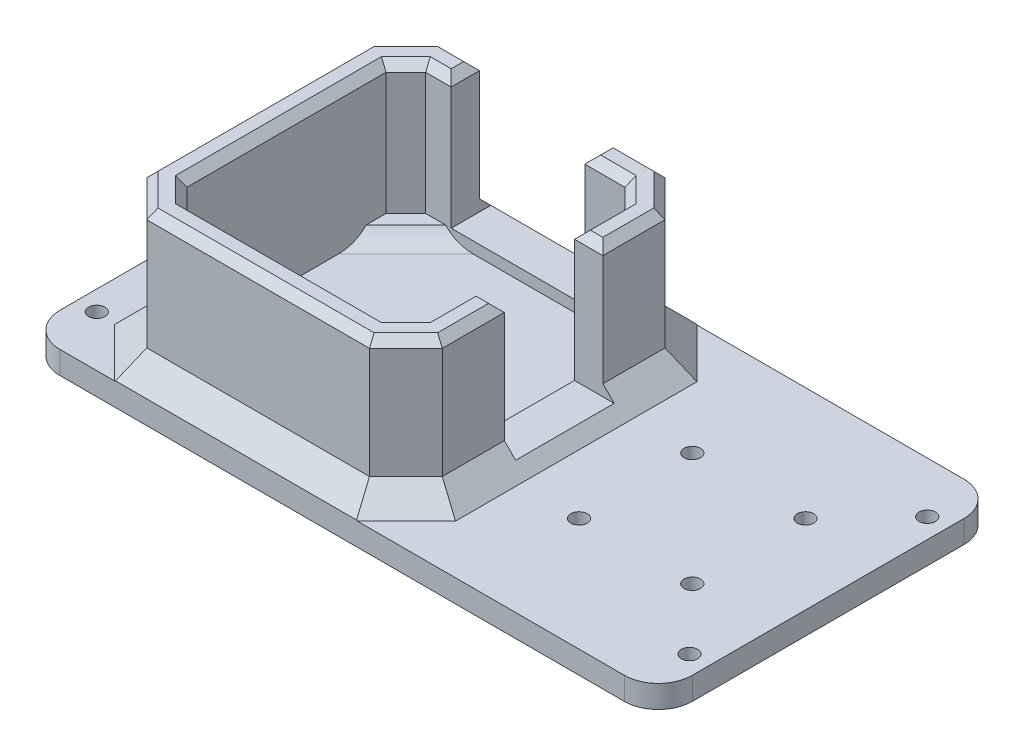
SolidWorks part; units mm, degrees
ref_plane "前视基准面" through (0, 0, 0) normal (0, 0, 1) x (1, 0, 0)
ref_plane "上视基准面" through (0, 0, 0) normal (0, 1, 0) x (1, 0, 0)
ref_plane "右视基准面" through (0, 0, 0) normal (1, 0, 0) x (0, 0, -1)
sketch "草图1" plane through (0, 0, 0) normal (0, 1, 0) x (1, 0, 0)
  line L1 (-52.35, -21) -> (52.35, -21) construction
  line L2 (-52.35, -21) -> (-52.35, 21) construction
  line L3 (-52.35, 21) -> (52.35, 21) construction
  line L4 (52.35, -21) -> (52.35, 21) construction
  line L5 (-52.35, -21) -> (52.35, 21) construction
  line L6 (-52.35, 21) -> (52.35, -21) construction
  line L7 (-55.85, -30) -> (55.85, -30)
  line L8 (-55.85, -30) -> (-55.85, 30)
  line L9 (-55.85, 30) -> (55.85, 30)
  line L10 (55.85, -30) -> (55.85, 30)
  line L11 (-55.85, -30) -> (55.85, 30) construction
  line L12 (-55.85, 30) -> (55.85, -30) construction
  circle A0 centre (-52.35, 21) radius 1.45
  circle A1 centre (52.35, 21) radius 1.45
  circle A2 centre (52.35, -21) radius 1.45
  circle A3 centre (-52.35, -21) radius 1.45
  point P0 (0, 0)
  point P10 (0, 0)
  dimension "D3" = 2.9
  dimension "D4" = 2.9
  dimension "D5" = 2.9
  dimension "D6" = 2.9
  dimension "D1" = 104.7
  dimension "D2" = 42
  dimension "D7" = 3.5
  dimension "D8" = 60
extrude "凸台-拉伸1" add sketch "草图1" along normal blind 4
sketch "草图2" plane through (0, 4, 0) normal (0, 1, 0) x (1, 0, 0)
  line L0 (-55.85, 30) -> (-55.85, -30) construction
  line L5 (-39.85, 21.1) -> (2.35, 21.1)
  line L6 (-39.85, 21.1) -> (-39.85, -21.1)
  line L7 (-39.85, -21.1) -> (2.35, -21.1)
  line L8 (2.35, 21.1) -> (2.35, -21.1)
  line L9 (-39.85, 21.1) -> (2.35, -21.1) construction
  line L10 (-39.85, -21.1) -> (2.35, 21.1) construction
  line L11 (-39.85, 17.6) -> (-36.35, 21.1)
  line L12 (-1.15, -21.1) -> (2.35, -17.6)
  line L13 (-39.85, -17.6) -> (-36.35, -21.1)
  line L14 (-1.15, 21.1) -> (2.35, 17.6)
  point P0 (-18.75, 0)
  dimension "D1" = 42.2
  dimension "D2" = 42.2
  dimension "D3" = 16
  dimension "D4" = 3.5
  dimension "D5" = 3.5
  dimension "D6" = 3.5
  dimension "D7" = 3.5
sketch "草图3" plane through (0, 4, 0) normal (0, 1, 0) x (1, 0, 0)
  line L0 (-1.15, 21.1) -> (2.35, 17.6) construction
  line L1 (-1.15, -21.1) -> (2.35, -17.6) construction
  line L2 (-39.85, -17.6) -> (-36.35, -21.1) construction
  line L3 (-39.85, 17.6) -> (-36.35, 21.1) construction
  line L4 (-1.15, 21.1) -> (2.35, 17.6)
  line L5 (-1.15, -21.1) -> (2.35, -17.6)
  line L6 (-39.85, -17.6) -> (-36.35, -21.1)
  line L7 (-39.85, 17.6) -> (-36.35, 21.1)
  line L8 (-39.85, 17.6) -> (-39.85, -17.6)
  line L9 (-36.35, -21.1) -> (-1.15, -21.1)
  line L10 (-36.35, 21.1) -> (-1.15, 21.1)
  line L11 (2.35, 17.6) -> (2.35, -17.6)
  line L12 (2.35, 17.6) -> (2.35, -17.6)
  line L13 (-1.15, -21.1) -> (2.35, -17.6)
  line L14 (-36.35, -21.1) -> (-1.15, -21.1)
  line L15 (-39.85, -17.6) -> (-36.35, -21.1)
  line L16 (-39.85, 17.6) -> (-39.85, -17.6)
  line L17 (-39.85, 17.6) -> (-36.35, 21.1)
  line L18 (-36.35, 21.1) -> (-1.15, 21.1)
  line L19 (-1.15, 21.1) -> (2.35, 17.6)
  line L20 (7.35, 19.6711) -> (7.35, -19.6711)
  line L21 (0.9211, -26.1) -> (7.35, -19.6711)
  line L22 (-38.4211, -26.1) -> (0.9211, -26.1)
  line L23 (-44.85, -19.6711) -> (-38.4211, -26.1)
  line L24 (-44.85, 19.6711) -> (-44.85, -19.6711)
  line L25 (-44.85, 19.6711) -> (-38.4211, 26.1)
  line L26 (-38.4211, 26.1) -> (0.9211, 26.1)
  line L27 (0.9211, 26.1) -> (7.35, 19.6711)
  line L30 (-31.8391, 21.1) -> (-31.8391, 26.1)
  line L32 (-8.2391, 21.1) -> (-8.2391, 26.1)
  line L33 (-18.75, 21.1) -> (-6.95, 25.2863) construction
  line L34 (-30.55, 25.2863) -> (-18.75, 21.1) construction
  line L35 (2.35, -8.7) -> (7.35, -8.7)
  line L37 (2.35, 8.7) -> (7.35, 8.7)
  line L39 (2.35, 0) -> (8.8507, 8.7) construction
  line L40 (2.35, 0) -> (8.8507, -8.7) construction
  point P24 (-18.75, 21.1)
  point P29 (2.35, 0)
  dimension "D3" = 23.6
  dimension "D4" = 17.4
  dimension "D1" = 0
  dimension "D2" = 5
extrude "凸台-拉伸2" add sketch "草图3" along normal blind 25 contours L35 L12 L5 L9 L6 L8 L7 L10 L30 L26 L25 L24 L23 L22 L21 L20 | L11 L37 L20 L27 L26 L32 L10 L4 region at (1.3213, 4, -19.0608) region at (-34.0945, 4, -21.8382)
sketch "草图4" plane through (0, 4, 0) normal (0, 1, 0) x (1, 0, 0)
  line L0 (7.35, -8.7) -> (2.35, -8.7) construction
  line L1 (2.35, -8.7) -> (2.35, -17.6) construction
  line L2 (2.35, -17.6) -> (-1.15, -21.1) construction
  line L3 (-1.15, -21.1) -> (-36.35, -21.1) construction
  line L4 (-36.35, -21.1) -> (-39.85, -17.6) construction
  line L5 (-39.85, -17.6) -> (-39.85, 17.6) construction
  line L6 (-39.85, 17.6) -> (-36.35, 21.1) construction
  line L7 (-36.35, 21.1) -> (-31.8391, 21.1) construction
  line L8 (-31.8391, 21.1) -> (-31.8391, 26.1) construction
  line L9 (-31.8391, 26.1) -> (-38.4211, 26.1) construction
  line L10 (-38.4211, 26.1) -> (-44.85, 19.6711) construction
  line L11 (-44.85, 19.6711) -> (-44.85, -19.6711) construction
  line L12 (-44.85, -19.6711) -> (-38.4211, -26.1) construction
  line L13 (-38.4211, -26.1) -> (0.9211, -26.1) construction
  line L14 (0.9211, -26.1) -> (7.35, -19.6711) construction
  line L15 (7.35, -19.6711) -> (7.35, -8.7) construction
  line L16 (2.35, 17.6) -> (2.35, 8.7) construction
  line L17 (2.35, 8.7) -> (7.35, 8.7) construction
  line L18 (7.35, 8.7) -> (7.35, 19.6711) construction
  line L19 (7.35, 19.6711) -> (0.9211, 26.1) construction
  line L20 (0.9211, 26.1) -> (-8.2391, 26.1) construction
  line L21 (-8.2391, 26.1) -> (-8.2391, 21.1) construction
  line L22 (-8.2391, 21.1) -> (-1.15, 21.1) construction
  line L23 (-1.15, 21.1) -> (2.35, 17.6) construction
  line L24 (7.35, -8.7) -> (2.35, -8.7)
  line L25 (2.35, -8.7) -> (2.35, -17.6)
  line L26 (2.35, -17.6) -> (-1.15, -21.1)
  line L27 (-1.15, -21.1) -> (-36.35, -21.1)
  line L28 (-36.35, -21.1) -> (-39.85, -17.6)
  line L29 (-39.85, -17.6) -> (-39.85, 17.6)
  line L30 (-39.85, 17.6) -> (-36.35, 21.1)
  line L31 (-36.35, 21.1) -> (-31.8391, 21.1)
  line L32 (-31.8391, 21.1) -> (-31.8391, 26.1)
  line L33 (-31.8391, 26.1) -> (-38.4211, 26.1)
  line L34 (-38.4211, 26.1) -> (-44.85, 19.6711)
  line L35 (-44.85, 19.6711) -> (-44.85, -19.6711)
  line L36 (-44.85, -19.6711) -> (-38.4211, -26.1)
  line L37 (-38.4211, -26.1) -> (0.9211, -26.1)
  line L38 (0.9211, -26.1) -> (7.35, -19.6711)
  line L39 (7.35, -19.6711) -> (7.35, -8.7)
  line L40 (2.35, 17.6) -> (2.35, 8.7)
  line L41 (2.35, 8.7) -> (7.35, 8.7)
  line L42 (7.35, 8.7) -> (7.35, 19.6711)
  line L43 (7.35, 19.6711) -> (0.9211, 26.1)
  line L44 (0.9211, 26.1) -> (-8.2391, 26.1)
  line L45 (-8.2391, 26.1) -> (-8.2391, 21.1)
  line L46 (-8.2391, 21.1) -> (-1.15, 21.1)
  line L47 (-1.15, 21.1) -> (2.35, 17.6)
  line L48 (-32.7789, 21.1) -> (-39.85, 14.0289)
  line L49 (-39.85, -14.0289) -> (-32.7789, -21.1)
  line L50 (-4.7211, -21.1) -> (2.35, -14.0289)
  line L51 (-4.7211, 21.1) -> (2.35, 14.0289)
  line L53 (2.35, 8.7) -> (7.35, 8.7)
  line L54 (2.35, 8.7) -> (2.35, -8.7)
  line L55 (2.35, -8.7) -> (7.35, -8.7)
  line L56 (7.35, 8.7) -> (7.35, -8.7)
  line L57 (-8.2391, 21.1) -> (-31.8391, 21.1)
  line L58 (-8.2391, 21.1) -> (-8.2391, 26.1)
  line L59 (-8.2391, 26.1) -> (-31.8391, 26.1)
  line L60 (-31.8391, 21.1) -> (-31.8391, 26.1)
  line M17 (2.35, -17.6) -> (2.35, -8.7)
  line M18 (2.35, -8.7) -> (7.35, -8.7)
  line M26 (-31.8391, 26.1) -> (-31.8391, 21.1)
  line M28 (-36.35, 21.1) -> (-39.85, 17.6)
  line M29 (-39.85, 17.6) -> (-39.85, -17.6)
  line M30 (-39.85, -17.6) -> (-36.35, -21.1)
  line M31 (-36.35, -21.1) -> (-1.15, -21.1)
  line M32 (-1.15, -21.1) -> (2.35, -17.6)
  line M34 (2.35, 17.6) -> (-1.15, 21.1)
  line M35 (-1.15, 21.1) -> (-8.2391, 21.1)
  line M36 (-8.2391, 21.1) -> (-8.2391, 26.1)
  line M40 (7.35, 8.7) -> (2.35, 8.7)
  dimension "D1" = 10
  dimension "D2" = 10
  dimension "D3" = 10
  dimension "D4" = 10
extrude "凸台-拉伸3" add sketch "草图4" along normal blind 2 contours L59 L57 M36 M26 | L56 L54 M40 M18 | L48 L31 M28 M29 | L51 L40 M35 M34 | L50 M31 M32 M17 | L49 M29 M30 M31 region at (4.85, 4, 0) region at (-0.3933, 4, 18.3567) region at (-0.3933, 4, -18.3567) region at (-37.1067, 4, 18.3567) region at (-20.0391, 4, -23.6) region at (-37.1067, 4, -18.3567)
chamfer "倒角1" distance 4 angle 45 8 edges at (-41.6355, 4, -22.8855) (-18.75, 4, -26.1) (4.1355, 4, -22.8855) (-44.85, 4, 0) (-41.6355, 4, 22.8855) (7.35, 4, 0) (4.1355, 4, 22.8855) (-18.75, 4, 26.1)
fillet "圆角1" radius 6 4 edges at (-55.85, 2, -30) (55.85, 2, -30) (55.85, 2, 30) (-55.85, 2, 30)
sketch "草图5" plane through (0, 4, 0) normal (0, 1, 0) x (1, 0, 0)
  line L0 (55.85, 0) -> (9.35, 0) construction
  line L1 (55.85, -24) -> (55.85, 24) construction
  line L2 (9.35, -8.7) -> (9.35, 8.7) construction
  circle A0 centre (21.85, 10) radius 1.45
  circle A1 centre (41.85, 10) radius 1.45
  circle A2 centre (41.85, -10) radius 1.45
  circle A3 centre (21.85, -10) radius 1.45
  dimension "D1" = 2.9
  dimension "D2" = 2.9
  dimension "D3" = 14
  dimension "D4" = 20
  dimension "D5" = 10
extrude "切除-拉伸1" cut sketch "草图5" against normal through all
chamfer "倒角2" distance 1.4 angle 45 24 edges at (0.6, 29, -19.35) (-4.6945, 29, -21.1) (-8.2391, 29, -23.6) (2.35, 29, -13.15) (4.85, 29, -8.7) (7.35, 29, -14.1855) (4.1355, 29, -22.8855) (-3.659, 29, -26.1) (-31.8391, 29, -23.6) (-34.0945, 29, -21.1) (-38.1, 29, -19.35) (-39.85, 29, 0) (-38.1, 29, 19.35) (-18.75, 29, 21.1) (0.6, 29, 19.35) (2.35, 29, 13.15) (4.85, 29, 8.7) (7.35, 29, 14.1855) (4.1355, 29, 22.8855) (-35.1301, 29, -26.1) (-41.6355, 29, -22.8855) (-18.75, 29, 26.1) (-44.85, 29, 0) (-41.6355, 29, 22.8855)
fillet "圆角2" radius 4 4 edges at (-36.3145, 4, 17.5645) (-36.3145, 4, -17.5645) (-1.1855, 4, -17.5645) (-1.1855, 4, 17.5645)
